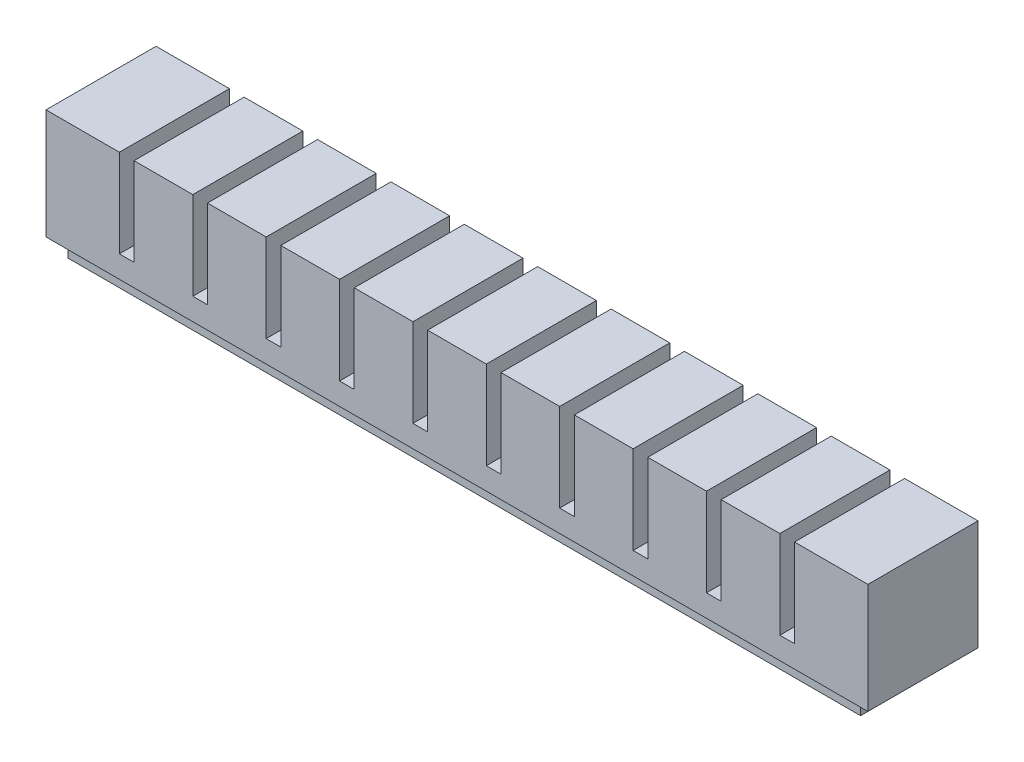
SolidWorks part; units mm, degrees
ref_plane "Front Plane" through (0, 0, 0) normal (0, 0, 1) x (1, 0, 0)
ref_plane "Top Plane" through (0, 0, 0) normal (0, 1, 0) x (1, 0, 0)
ref_plane "Right Plane" through (0, 0, 0) normal (1, 0, 0) x (0, 0, -1)
sketch "Sketch1" plane through (0, 0, 0) normal (0, 0, 1) x (1, 0, 0)
  line L1 (0, 0) -> (8, 0)
  line L2 (0, 0) -> (0, 15)
  line L3 (0, 15) -> (8, 15)
  line L4 (8, 0) -> (8, 15)
  dimension "D1" = 8
  dimension "D2" = 15
extrude "first chamber block" add sketch "Sketch1" along normal blind 15
sketch "Sketch2" plane through (0, 0, 0) normal (0, -1, 0) x (1, 0, 0)
  line L0 (8, 15) -> (8, 0) construction
  line L1 (1, 13) -> (7, 13)
  line L2 (1, 13) -> (1, 2)
  line L3 (1, 2) -> (7, 2)
  line L4 (7, 13) -> (7, 2)
  line L5 (0, 15) -> (0, 0) construction
  line L6 (0, 15) -> (8, 15) construction
  line L7 (0, 0) -> (8, 0) construction
  dimension "D1" = 1
  dimension "D2" = 1
  dimension "D3" = 2
  dimension "D4" = 2
extrude "first chamber cavity" cut sketch "Sketch2" against normal blind 13
sketch "Sketch3" plane through (8, 0, 0) normal (1, 0, 0) x (0, 0, -1)
  line L0 (-15, 0) -> (-15, 15) construction
  line L1 (0, 0) -> (-15, 0)
  line L2 (0, 0) -> (0, 3)
  line L3 (0, 3) -> (-15, 3)
  line L4 (-15, 0) -> (-15, 3)
  dimension "D1" = 3
extrude "chamber spacer" add sketch "Sketch3" along normal blind 2
pattern_linear "pattern chambers" count 11 spacing 10 along (1, 0, 0) of "chamber spacer", "first chamber cavity", "first chamber block"
combine bodies "combine into 1 solid body" operation type add bodies to combine 123 122 121 120 119 118 117 116 115 114 103
sketch "Sketch4" plane through (108, 0, 0) normal (1, 0, 0) x (0, 0, -1)
  line L1 (0, 15) -> (-15, 15)
  line L2 (0, 15) -> (0, 3)
  line L3 (0, 3) -> (-15, 3)
  line L4 (-15, 15) -> (-15, 3)
extrude "thicken end 1" add sketch "Sketch4" along normal up to surface (2 mm away) up to face at (110, 1.5, 7.5)
sketch "Sketch5" plane through (0, 0, 0) normal (-1, 0, 0) x (0, 0, 1)
  line L1 (15, 15) -> (0, 15)
  line L2 (15, 15) -> (15, 0)
  line L3 (15, 0) -> (0, 0)
  line L4 (0, 15) -> (0, 0)
extrude "thicken end 2" add sketch "Sketch5" along normal blind 2
ref_point "center of bottom face"
sketch "Sketch6" plane through (0, 0, 0) normal (0, -1, 0) x (1, 0, 0)
  line L0 (7, 2) -> (7, 13) construction
  line L1 (101, 6.5) -> (7, 6.5)
  line L2 (101, 6.5) -> (101, 8.5)
  line L3 (101, 8.5) -> (7, 8.5)
  line L4 (7, 6.5) -> (7, 8.5)
  line L5 (101, 6.5) -> (7, 8.5) construction
  line L6 (101, 8.5) -> (7, 6.5) construction
  point P0 (54, 7.5)
  dimension "D1" = 2
extrude "central air channel" cut sketch "Sketch6" against normal blind 2
sketch "Sketch7" plane through (0, 0, 0) normal (0, -1, 0) x (1, 0, 0)
  line L0 (0, 14) -> (108, 14)
  line L1 (1, 13) -> (107, 13)
  line L2 (1, 13) -> (1, 2)
  line L3 (1, 2) -> (107, 2)
  line L4 (107, 13) -> (107, 2)
  line L5 (108, 14) -> (108, 1)
  line L6 (0, 1) -> (108, 1)
  line L7 (0, 14) -> (0, 1)
  dimension "D1" = 1
extrude "bonding ridge" add sketch "Sketch7" along normal blind 2
sketch "Sketch9" plane through (0, 0, 0) normal (0, -1, 0) x (1, 0, 0)
  line L0 (11, 8.5) -> (11, 13) construction
  line L1 (11, 13) -> (7, 13) construction
  line L2 (7, 13) -> (7, 8.5) construction
  line L3 (7, 8.5) -> (11, 8.5) construction
  line L4 (7, 6.5) -> (7, 2) construction
  line L5 (7, 2) -> (11, 2) construction
  line L6 (11, 2) -> (11, 6.5) construction
  line L7 (11, 6.5) -> (7, 6.5) construction
  line L8 (11, 8.5) -> (11, 13) construction
  line L9 (11, 13) -> (7, 13) construction
  line L10 (7, 13) -> (7, 8.5) construction
  line L11 (7, 8.5) -> (11, 8.5) construction
  line L12 (7, 6.5) -> (7, 2) construction
  line L13 (7, 2) -> (11, 2) construction
  line L14 (11, 2) -> (11, 6.5) construction
  line L15 (11, 6.5) -> (7, 6.5) construction
  line L16 (10, 9.5) -> (10, 12)
  line L17 (10, 12) -> (8, 12)
  line L18 (8, 12) -> (8, 9.5)
  line L19 (8, 9.5) -> (10, 9.5)
  line L20 (8, 5.5) -> (8, 3)
  line L21 (8, 3) -> (10, 3)
  line L22 (10, 3) -> (10, 5.5)
  line L23 (10, 5.5) -> (8, 5.5)
  dimension "D1" = 1
extrude "bonding bumps" add sketch "Sketch9" along normal blind 2
pattern_linear "pattern bonding bumps" count 10 spacing 10 along (1, 0, 0) of "bonding bumps"
